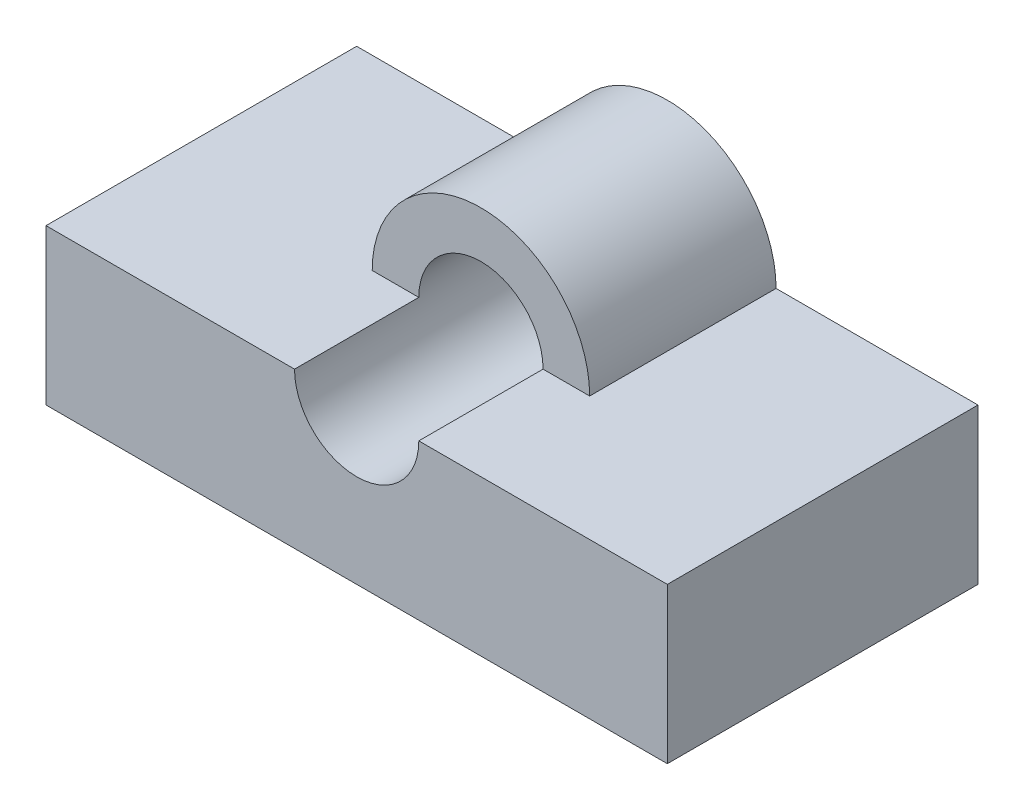
SolidWorks part; units mm, degrees
material "Plain Carbon Steel"
ref_plane "Front Plane" through (0, 0, 0) normal (0, 0, 1) x (1, 0, 0)
ref_plane "Top Plane" through (0, 0, 0) normal (0, 1, 0) x (1, 0, 0)
ref_plane "Right Plane" through (0, 0, 0) normal (1, 0, 0) x (0, 0, -1)
sketch "Sketch1" plane through (0, 0, 0) normal (0, 0, 1) x (1, 0, 0)
  line L1 (0, 0) -> (100, 0)
  line L2 (0, 0) -> (0, 25)
  line L3 (0, 25) -> (100, 25)
  line L4 (100, 0) -> (100, 25)
  circle A0 centre (50, 25) radius 17.5
  circle A1 centre (50, 25) radius 10
  dimension "D3" = 35
  dimension "D4" = 20
  dimension "D1" = 100
  dimension "D2" = 25
extrude "Boss-Extrude1" add sketch "Sketch1" along normal blind 50 contours A0 L3 L2 L1 L4 | A1 L3 A0 region at (1.0308, 12.5, 0) region at (36.25, 24.6087, 0)
extrude "Boss-Extrude2" add sketch "Sketch1<3>" along normal blind 30 contours A1 L3 A0 | A1 L3 A0 region at (50, 42.1087, 0) region at (36.25, 24.6087, 0)
sketch "Sketch1<3>" plane through (0, 0, 0) normal (0, 0, 1) x (1, 0, 0) same geometry as "Sketch1"
